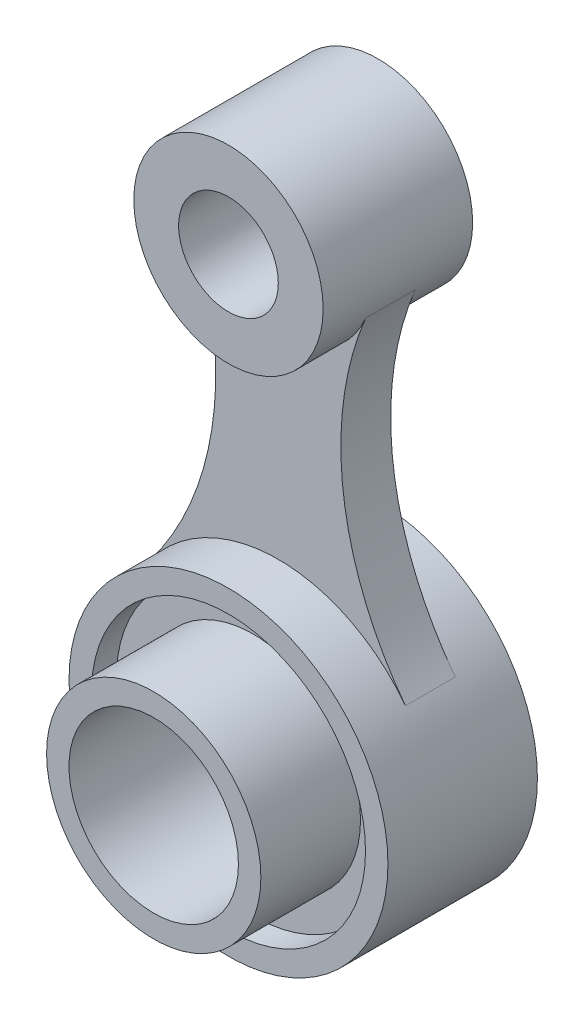
SolidWorks part; units mm, degrees
ref_plane "Front Plane" through (0, 0, 0) normal (0, 0, 1) x (1, 0, 0)
ref_plane "Top Plane" through (0, 0, 0) normal (0, 1, 0) x (1, 0, 0)
ref_plane "Right Plane" through (0, 0, 0) normal (1, 0, 0) x (0, 0, -1)
sketch "Sketch1" plane through (0, 0, 0) normal (1, 0, 0) x (0, 0, -1)
  line L0 (0, 17) -> (45, 17)
  line L1 (45, 17) -> (45, 32)
  line L2 (45, 32) -> (15, 32)
  line L3 (15, 32) -> (15, 21.5)
  line L4 (15, 21.5) -> (0, 21.5)
  line L5 (0, 21.5) -> (0, 17)
  line L6 (0, 0) -> (99.5462, 0) construction
  dimension "D1" = 21.5
  dimension "D2" = 17
  dimension "D3" = 32
  dimension "D4" = 30
  dimension "D5" = 45
revolve "Revolve1" add sketch "Sketch1" angle 360 about L6
sketch "Sketch2" plane through (0, 0, -15) normal (0, 0, 1) x (1, 0, 0)
  circle A0 centre (0, 0) radius 21.5 construction
  circle A1 centre (0, 0) radius 21.5
  circle A2 centre (0, 0) radius 27.5
  dimension "55" = 55
extrude "Cut-Extrude1" cut sketch "Sketch2" against normal blind 5
ref_plane "Plane1" through (0, 0, -30) normal (0, 0, 1) x (1, 0, 0)
sketch "Sketch3" plane through (0, 0, -30) normal (0, 0, 1) x (1, 0, 0)
  circle A0 centre (0, 90) radius 19
  circle A1 centre (0, 90) radius 10
  point P3 (0, 0)
  dimension "D1" = 38
  dimension "D2" = 20
  dimension "D3" = 90
extrude "Boss-Extrude1" add sketch "Sketch3" along normal blind 15 and the other way blind 15 separate body
sketch "Sketch4" plane through (0, 0, -30) normal (0, 0, 1) x (1, 0, 0)
  circle A0 centre (0, 0) radius 32 construction
  circle A1 centre (0, 90) radius 19 construction
  arc A2 (25.5177, 19.3093) -> (-25.5177, 19.3093) centre (0, 0) ccw
  arc A3 (-17.5242, 82.6582) -> (17.5242, 82.6582) centre (0, 90) ccw
  arc A4 (-25.5177, 19.3093) -> (-17.5242, 82.6582) centre (-76.5531, 57.9278) ccw
  arc A5 (17.5242, 82.6582) -> (25.5177, 19.3093) centre (76.5531, 57.9278) ccw
  dimension "D1" = 128
  dimension "D2" = 128
extrude "Boss-Extrude2" add sketch "Sketch4" along normal blind 5 and the other way blind 5
